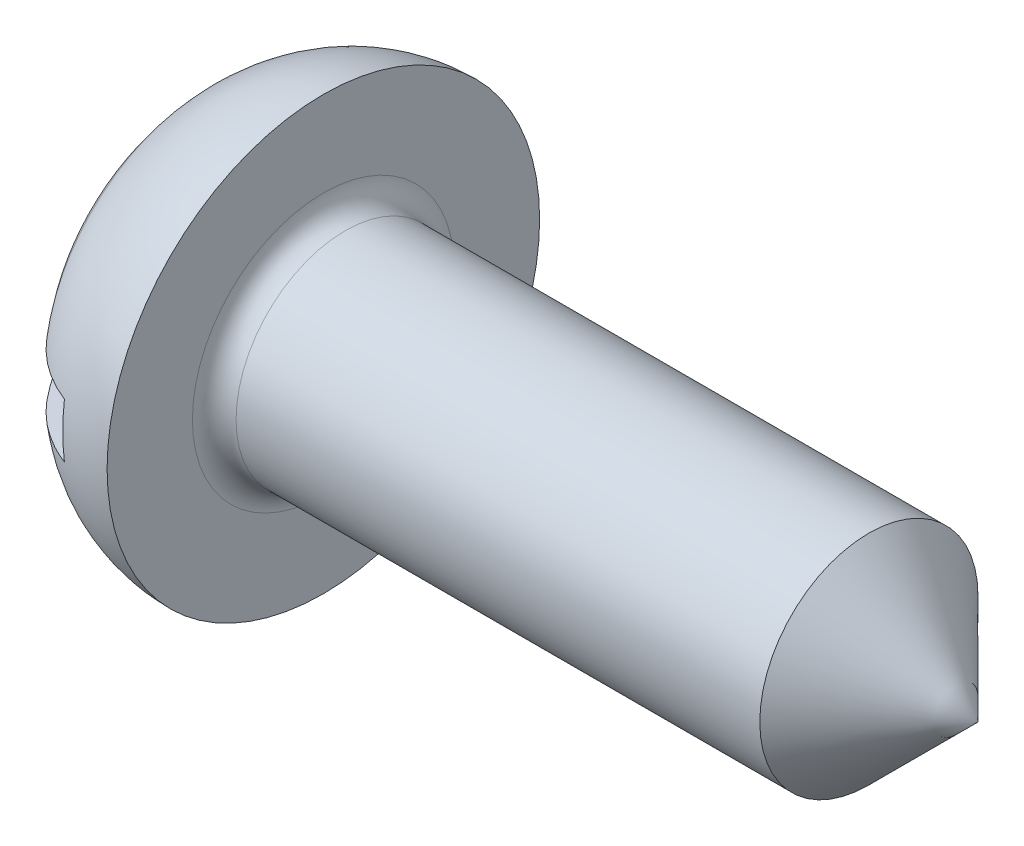
SolidWorks part; units mm, degrees
ref_plane "Front" through (0, 0, 0) normal (0, 0, 1) x (1, 0, 0)
ref_plane "Top" through (0, 0, 0) normal (0, 1, 0) x (1, 0, 0)
ref_plane "Right" through (0, 0, 0) normal (1, 0, 0) x (0, 0, -1)
sketch "Sketch2" plane through (2.3892, 0, -0.4071) normal (0, 1, 0) x (0, 0, -1)
  line L0 (-0.4071, 0.7892) -> (-0.4071, 1.2892)
  line L2 (-0.4071, 1.2892) -> (-0.1571, 1.2892)
  line L3 (-0.1571, 1.2892) -> (-0.1571, 2.3892)
  line L4 (-0.4071, 0.7892) -> (1.5751, 0.7892)
  line L5 (-0.4071, -1.008) -> (-0.4071, 3.8043) construction
  arc A0 (-0.1571, 2.3892) -> (1.0806, 1.8569) centre (-0.4071, 0.1029) cw
  arc A1 (1.5751, 0.7892) -> (1.0806, 1.8569) centre (0.1751, 0.7892) ccw
  dimension "r1" = 2.3
  dimension "r2" = 1.4
  dimension "t" = 1.1
  dimension "n" = 0.5
  dimension "k" = 1.6
revolve "BaseHead" add sketch "Sketch2" angle 360 about L5
sketch "Sketch1" plane through (1.6, 0.5923, -0.1734) normal (1, 0, 0) x (0, 0, -1)
  circle A0 centre (-0.1734, -0.5923) radius 1
  circle A1 centre (-0.1734, -0.5923) radius 1.9821 construction
extrude "BaseBody" add sketch "Sketch1" along normal blind 6
cosmetic thread "ThreadCosmetic1" [suppressed] parameters "D1"=3, "D2"=1.5
sketch "Sketch3" plane through (1.1978, 1.1978, 0) normal (0, 0, 1) x (0, 1, 0)
  line L0 (-0.9478, 0.0978) -> (-0.9478, 1.1978) construction
  line L1 (-0.9478, 0.0978) -> (-0.9478, 1.1978)
  line L2 (-1.4478, 1.1978) -> (-1.4478, 0.0978) construction
  line L3 (-1.4478, 1.1978) -> (-1.4478, 0.0978)
  line L4 (-1.1978, 0.0526) -> (-1.1978, 2.3431) construction
  line L5 (-1.4478, 1.1978) -> (-0.9478, 1.1978)
  line L6 (-1.4478, 0.0978) -> (-0.9478, 0.0978)
extrude "Slot" cut sketch "Sketch3" against normal through all and the other way through all
sketch "Sketch4" plane through (23.2633, -6.7367, 0) normal (0, 0, 1) x (0, 1, 0)
  line L0 (6.7367, 17.6285) -> (6.7367, 14.19) construction
  line L1 (7.7367, 15.6633) -> (7.7367, 21.6633) construction
  line L3 (8.7367, 14.6633) -> (8.7367, 17.6633)
  line L4 (8.7367, 17.6633) -> (6.7367, 15.6633)
  line L5 (6.7367, 15.6633) -> (6.7367, 14.6633)
  line L6 (6.7367, 14.6633) -> (8.7367, 14.6633)
  line L7 (5.7367, 15.6633) -> (7.7367, 15.6633) construction
  dimension "D1" = 1
  dimension "D2" = 45
  dimension "D3" = 1
revolve "Cut-Revolve1" cut sketch "Sketch4" angle 360 about L0
fillet "Fillet1" radius 0.2 1 edges at (1.6, 0, -1)
sketch "Sketch5" plane through (0, 0, 0) normal (0, 0, 1) x (1, 0, 0)
  line L0 (3.6, 1.2) -> (3.85, 1.2)
  line L1 (3.85, 1.2) -> (3.85, 1)
  line L2 (3.85, 1) -> (3.725, 0.7835)
  line L3 (3.6, 1) -> (3.725, 0.7835)
  line L4 (3.6, 1.2) -> (3.6, 1)
  line L5 (21.5487, 0) -> (0, 0) construction
  line L6 (3.6, 1) -> (3.85, 1) construction
  line L7 (3.725, 1) -> (3.725, 0.7835) construction
  line L8 (6.6, 1) -> (1.8, 1) construction
  point P6 (3.725, 1.2)
  dimension "D3" = 4
revolve "Cut-Revolve10" [suppressed] cut sketch "Sketch5" angle 360 about L5
pattern_linear "LPattern10" [suppressed] count 8 spacing 0.5 of bodies 105
equation "\"D3@Sketch5\" = \"D1@ThreadCosmetic1\" + \"d@Sketch1\" / 2"
equation "\"D2@Sketch5\" = (  \"d@Sketch1\" - \"D2@ThreadCosmetic1\" )  / 2"
equation "\"D3@LPattern10\" = \"D2@Sketch5\" * 2"
equation "\"D1@LPattern10\" = \"D3@Sketch5\" / \"D3@LPattern10\""
